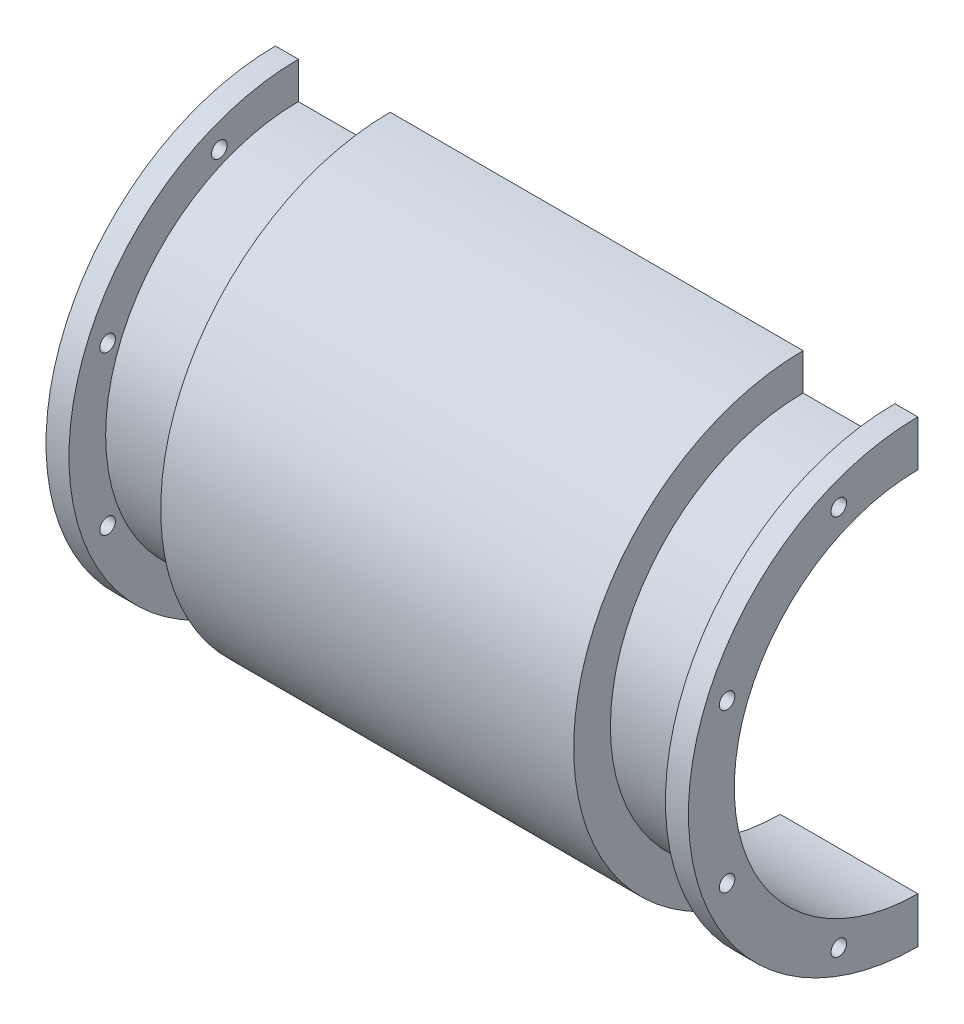
SolidWorks part; units mm, degrees
ref_plane "正面" through (0, 0, 0) normal (0, 0, 1) x (1, 0, 0)
ref_plane "平面" through (0, 0, 0) normal (0, 1, 0) x (1, 0, 0)
ref_plane "右側面" through (0, 0, 0) normal (1, 0, 0) x (0, 0, -1)
sketch "ｽｹｯﾁ1" plane through (0, 0, 0) normal (0, 0, 1) x (1, 0, 0)
  line L0 (-70, 40) -> (-40, 40)
  line L1 (-40, 40) -> (-40, 49)
  line L2 (-40, 49) -> (40, 49)
  line L3 (40, 49) -> (40, 40)
  line L4 (40, 40) -> (70, 40)
  line L5 (70, 40) -> (70, 50)
  line L6 (70, 50) -> (65, 50)
  line L7 (65, 50) -> (65, 42)
  line L8 (65, 42) -> (45, 42)
  line L9 (45, 42) -> (45, 50)
  line L10 (45, 50) -> (-45, 50)
  line L11 (-45, 50) -> (-45, 42)
  line L12 (-45, 42) -> (-65, 42)
  line L13 (-65, 42) -> (-65, 50)
  line L14 (-65, 50) -> (-70, 50)
  line L15 (-70, 50) -> (-70, 40)
  point P3 (0, 49)
  point P18 (0, 50)
  dimension "D1" = 1
  dimension "D2" = 10
  dimension "D3" = 2
  dimension "D4" = 140
  dimension "D5" = 5
  dimension "D6" = 5
  dimension "D7" = 20
  dimension "D8" = 50
sketch "ｽｹｯﾁ2" plane through (0, 0, 0) normal (0, 0, 1) x (1, 0, 0)
  line L0 (-50, 0) -> (50, 0)
  point P3 (0, 0)
  dimension "D1" = 100
revolve "回転1" add sketch "ｽｹｯﾁ1" angle 180 about L0
hole_wizard "M3 すきま穴1" positions "ｽｹｯﾁ5" profile "ｽｹｯﾁ6" hole size "M3" standard "JIS" end condition up to next
sketch "ｽｹｯﾁ5" plane through (-70, 0, 0) normal (-1, 0, 0) x (0, 0, 1)
  line L5 (0, 0) -> (17.2208, -41.5746)
  line L7 (0, -50) -> (0, -40) construction
  circle A0 centre (0, 0) radius 40 construction
  point P0 (17.2208, -41.5746)
  dimension "D1" = 45
  dimension "D2" = 22.5
sketch "ｽｹｯﾁ6" plane through (-70, -41.5746, 17.2208) normal (0, 1, 0) x (0, 0, 1)
  line L0 (0, 0) -> (0, 5)
  line L1 (0, 5) -> (1.7, 5)
  line L2 (1.7, 5) -> (1.7, 0)
  line L5 (1.7, 0) -> (0, 0)
  line L11 (0, -6.35) -> (0, 107.95) construction
  dimension "通し穴の直径" = 3.4
  dimension "通し穴の深さ" = 5
pattern_circular "円形ﾊﾟﾀｰﾝ1" count 4 every 45 about axis through (-70, 0, 0) along (-1, 0, 0) of "M3 すきま穴1"
mirror "ﾐﾗｰ1" about plane through (0, 0, 0) normal (1, 0, 0) of "円形ﾊﾟﾀｰﾝ1"
fillet "ﾌｨﾚｯﾄ1" radius 9 2 edges at (-40, 0, 49) (40, 0, 49)
